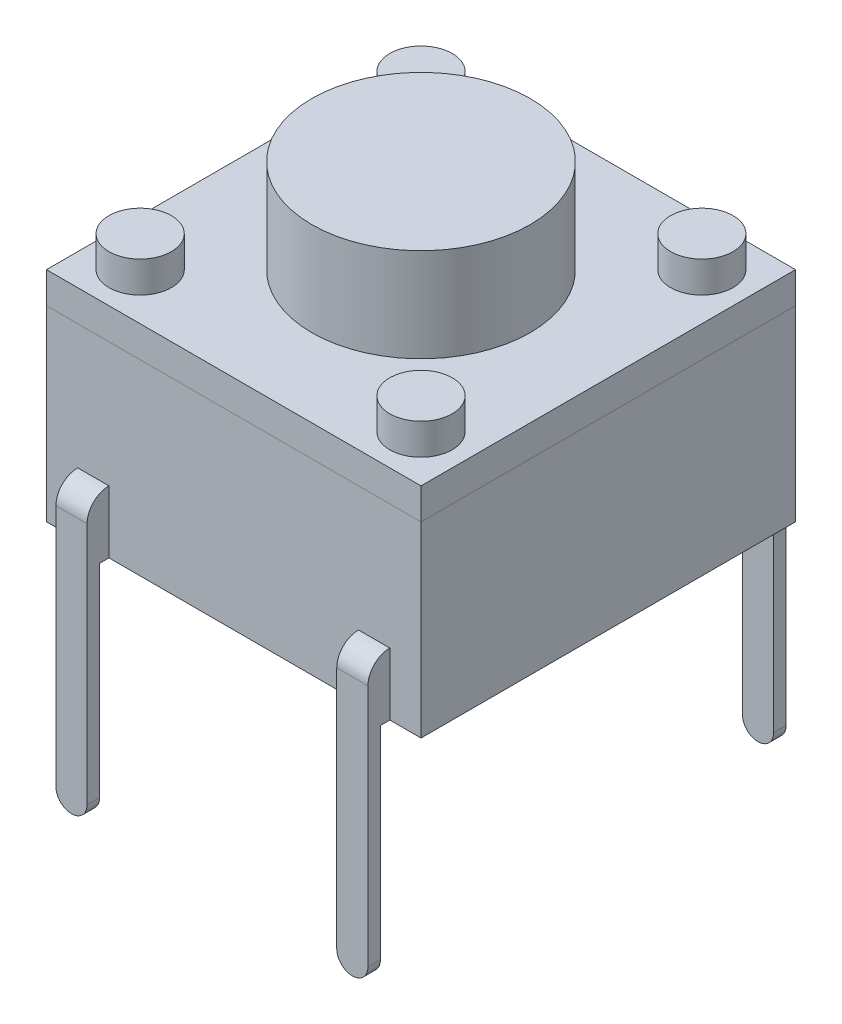
SolidWorks part; units mm, degrees
other "Cámara1"
ref_plane "Alzado" through (0, 0, 0) normal (0, 0, 1) x (1, 0, 0)
ref_plane "Planta" through (0, 0, 0) normal (0, 1, 0) x (1, 0, 0)
ref_plane "Vista lateral" through (0, 0, 0) normal (1, 0, 0) x (0, 0, -1)
sketch "Croquis3" plane through (0, 0, 0) normal (0, 1, 0) x (1, 0, 0)
  line L1 (3, -3) -> (-3, -3)
  line L2 (3, -3) -> (3, 3)
  line L3 (3, 3) -> (-3, 3)
  line L4 (-3, -3) -> (-3, 3)
  line L5 (3, -3) -> (-3, 3) construction
  line L6 (3, 3) -> (-3, -3) construction
  point P0 (0, 0)
  dimension "D1" = 6
  dimension "D2" = 6
extrude "Saliente-Extruir4" add sketch "Croquis3" along normal blind 3
ref_plane "Plano4" through (0, 3, 0) normal (0, 1, 0) x (1, 0, 0)
sketch "Croquis6" plane through (0, 3, 0) normal (0, 1, 0) x (1, 0, 0)
  line L1 (3.0005, -3.0005) -> (-3.0005, -3.0005)
  line L2 (3.0005, -3.0005) -> (3.0005, 3.0005)
  line L3 (3.0005, 3.0005) -> (-3.0005, 3.0005)
  line L4 (-3.0005, -3.0005) -> (-3.0005, 3.0005)
  line L5 (3.0005, -3.0005) -> (-3.0005, 3.0005) construction
  line L6 (3.0005, 3.0005) -> (-3.0005, -3.0005) construction
  point P0 (0, 0)
  dimension "D1" = 6.001
  dimension "D2" = 6.001
extrude "Saliente-Extruir9" add sketch "Croquis6" along normal blind 0.5
sketch "Croquis7" plane through (0, 3.5, 0) normal (0, 1, 0) x (1, 0, 0)
  line L0 (-3.0005, 3.0005) -> (3.0005, -3.0005) construction
  line L1 (0, 3.0005) -> (0, -3.0005) construction
  line L2 (3.0005, 3.0005) -> (-3.0005, -3.0005) construction
  line L3 (3.0005, 3.0005) -> (-3.0005, 3.0005) construction
  line L4 (-3.0005, -3.0005) -> (3.0005, -3.0005) construction
  line L6 (-3.0005, 3.0005) -> (-3.0005, -3.0005) construction
  line L7 (-3.0005, 0) -> (3.0005, 0) construction
  line L8 (3.0005, -3.0005) -> (3.0005, 3.0005) construction
  circle A0 centre (0, 0) radius 1.75
  circle A1 centre (-2.25, 2.25) radius 0.5
  circle A2 centre (2.25, 2.25) radius 0.5
  circle A3 centre (2.25, -2.25) radius 0.5
  circle A4 centre (-2.25, -2.25) radius 0.5
  dimension "D1" = 1
  dimension "D2" = 3.5
  dimension "D3" = 2.25
extrude "Saliente-Extruir10" add sketch "Croquis7" along normal blind 0.5 contours A4 | A1 | A2 | A3 region at (-2.25, 3.5, -2.25) region at (2.25, 3.5, -2.25) region at (2.25, 3.5, 2.25) region at (-2.25, 3.5, 2.25)
extrude "Saliente-Extruir11" add sketch "Croquis7<3>" along normal blind 1.5 contours A0 region at (0, 3.5, 0)
sketch "Croquis7<3>" plane through (0, 3.5, 0) normal (0, 1, 0) x (1, 0, 0) same geometry as "Croquis7"
sketch "Croquis8" plane through (0, 0, 3) normal (0, 0, 1) x (1, 0, 0)
  line L0 (0, 0) -> (0, 3) construction
  line L1 (-3, 0) -> (3, 0) construction
  line L2 (-3.0002, 3) -> (3.0003, 3) construction
  line L12 (-2.5, 1) -> (-2, 1)
  line L13 (-2.5, 1) -> (-2.5, -3.25)
  line L15 (-2, 1) -> (-2, -3.25)
  line L21 (2, 1) -> (2, -3.25)
  line L22 (2.5, 1) -> (2, 1)
  line L23 (2.5, 1) -> (2.5, -3.25)
  arc A0 (-2.5, -3.25) -> (-2, -3.25) centre (-2.25, -3.25) ccw
  arc A1 (2, -3.25) -> (2.5, -3.25) centre (2.25, -3.25) ccw
  point P10 (-2.25, -3.5)
  dimension "D4" = 0.5
  dimension "D1" = 1
  dimension "D2" = 0.5
  dimension "D3" = 3.5
extrude "Saliente-Extruir12" add sketch "Croquis8" along normal blind 0.35
fillet "Redondeo3" radius 0.35 2 edges at (-2.25, 1, 3.35) (2.25, 1, 3.35)
mirror "Simetría4" about plane through (0, 0, 0) normal (0, 0, 1) of "Redondeo3", "Saliente-Extruir12"
sketch "Croquis11" plane through (0, 0, 0) normal (0, -1, 0) x (1, 0, 0)
  line L1 (3, -3.15) -> (-3, -3.15)
  line L2 (3, -3.15) -> (3, 3.15)
  line L3 (3, 3.15) -> (-3, 3.15)
  line L4 (-3, -3.15) -> (-3, 3.15)
  line L5 (3, -3.15) -> (-3, 3.15) construction
  line L6 (3, 3.15) -> (-3, -3.15) construction
  point P0 (0, 0)
  dimension "D1" = 6
  dimension "D2" = 6.3
extrude "Cortar-Extruir1" cut sketch "Croquis11" along normal blind 6.2
